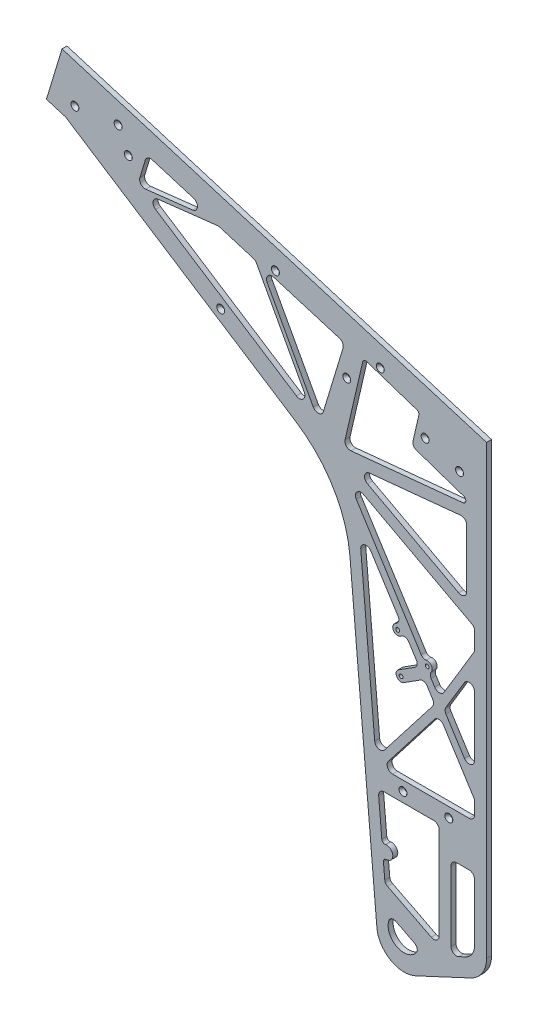
SolidWorks part; units mm, degrees
material "Beech"
ref_plane "Front Plane" through (0, 0, 0) normal (0, 0, 1) x (1, 0, 0)
ref_plane "Top Plane" through (0, 0, 0) normal (0, 1, 0) x (1, 0, 0)
ref_plane "Right Plane" through (0, 0, 0) normal (1, 0, 0) x (0, 0, -1)
sketch "Sketch2" plane through (0, 0, 0) normal (0, 0, 1) x (1, 0, 0)
  line L3 (52.061, -347.2658) -> (17.0528, -329.4943)
  line L18 (0.7275, -204.3995) -> (4.7586, -250.4747)
  line L19 (71, -196.7894) -> (7.7009, -196.7894)
  line L20 (78, -320.9929) -> (78, -203.7894)
  line L21 (8.8549, -297.2958) -> (67.8314, -327.2347)
  line L22 (6.8503, -274.3834) -> (8.8549, -297.2958)
  line L23 (11.4827, -269.9628) -> (10.4865, -270.05)
  line L24 (9.092, -254.1109) -> (10.0882, -254.0237)
  line L27 (123, -309.0696) -> (123, -235.7894)
  line L28 (102.9583, -331.1566) -> (111.4524, -327.1958)
  line L29 (93, -235.7894) -> (93, -324.8124)
  line L30 (116, -228.7894) -> (100, -228.7894)
  line L35 (123, -164.7894) -> (123, -147.491)
  line L36 (18.4936, -171.7894) -> (116, -171.7894)
  line L37 (71.9182, -84.5103) -> (12.9629, -160.4984)
  line L38 (123, -147.491) -> (83.3585, -85.0495)
  line L41 (123, -104.7468) -> (123, -28.6549)
  line L42 (86.5792, -71.4649) -> (110.0903, -108.4986)
  line L43 (110.0027, -25.0448) -> (86.4916, -64.103)
  line L47 (-22.0887, 56.3913) -> (-4.3233, -146.6681)
  line L48 (69.6883, -63.5168) -> (-9.2057, 60.7532)
  line L49 (8.1807, -150.3489) -> (69.3092, -71.5595)
  line L55 (84.1071, -48.674) -> (123, 15.9373)
  line L56 (-27.7256, 108.5825) -> (72.2002, -48.8158)
  line L57 (123, 42.7347) -> (-18.5117, 118.5054)
  line L58 (123, 15.9373) -> (123, 42.7347)
  line L61 (105.3136, 157.4535) -> (-10.9295, 145.9995)
  line L62 (113, 76.7923) -> (113, 150.4873)
  line L63 (-13.5473, 132.8622) -> (102.6958, 70.6213)
  line L71 (49.3928, 246.173) -> (-14.4833, 267.3378)
  line L72 (43.1791, 203.129) -> (52.0322, 241.4762)
  line L73 (109.2468, 180.5917) -> (43.1791, 203.129)
  line L74 (-34.5621, 158.7435) -> (108.3476, 172.8251)
  line L75 (-19.6388, 264.4406) -> (-42.0691, 167.2844)
  line L99 (-35.9297, 42.1538) -> (-1.5139, -351.2208)
  line L100 (48.0382, -379.8296) -> (118.2139, -347.1062)
  line L101 (138.3789, -315.4534) -> (138.3789, 254.5381)
  line L102 (138.3789, 254.5381) -> (-403.0991, 418.4193)
  line L103 (-403.0991, 418.4193) -> (-422.935, 352.8794)
  line L104 (-422.935, 352.8794) -> (-398.6241, 345.5216)
  line L105 (-398.6241, 345.5216) -> (-105.0266, 156.03)
  line L106 (-35.9297, 42.1538) -> (-1.5139, -351.2208)
  line L107 (48.0382, -379.8296) -> (118.2139, -347.1062)
  line L108 (138.3789, -315.4534) -> (138.3789, 254.5381)
  line L109 (138.3789, 254.5381) -> (-403.0991, 418.4193)
  line L110 (-403.0991, 418.4193) -> (-422.935, 352.8794)
  line L111 (-422.935, 352.8794) -> (-398.6241, 345.5216)
  line L112 (-398.6241, 345.5216) -> (-105.0266, 156.03)
  arc A2 (17.0528, -329.4943) -> (52.061, -347.2658) centre (32.8243, -341.7931) ccw
  arc A14 (4.7586, -250.4747) -> (9.092, -254.1109) centre (8.7434, -250.1261) ccw
  arc A15 (7.7009, -196.7894) -> (0.7275, -204.3995) centre (7.7009, -203.7894) ccw
  arc A16 (78, -203.7894) -> (71, -196.7894) centre (71, -203.7894) ccw
  arc A17 (67.8314, -327.2347) -> (78, -320.9929) centre (71, -320.9929) ccw
  arc A18 (10.4865, -270.05) -> (6.8503, -274.3834) centre (10.8351, -274.0347) ccw
  arc A19 (11.4827, -269.9628) -> (10.0882, -254.0237) centre (10.7854, -261.9933) ccw
  arc A22 (123, -235.7894) -> (116, -228.7894) centre (116, -235.7894) ccw
  arc A23 (111.4524, -327.1958) -> (123, -309.0696) centre (103, -309.0696) ccw
  arc A24 (93, -324.8124) -> (102.9583, -331.1566) centre (100, -324.8124) ccw
  arc A25 (100, -228.7894) -> (93, -235.7894) centre (100, -235.7894) ccw
  arc A28 (116, -171.7894) -> (123, -164.7894) centre (116, -164.7894) ccw
  arc A29 (12.9629, -160.4984) -> (18.4936, -171.7894) centre (18.4936, -164.7894) ccw
  arc A30 (83.3585, -85.0495) -> (71.9182, -84.5103) centre (77.4488, -88.8013) ccw
  arc A34 (110.0903, -108.4986) -> (123, -104.7468) centre (116, -104.7468) ccw
  arc A35 (86.4916, -64.103) -> (86.5792, -71.4649) centre (92.4888, -67.7131) ccw
  arc A36 (123, -28.6549) -> (110.0027, -25.0448) centre (116, -28.6549) ccw
  arc A40 (-4.3233, -146.6681) -> (8.1807, -150.3489) centre (2.65, -146.058) ccw
  arc A41 (-9.2057, 60.7532) -> (-22.0887, 56.3913) centre (-15.1153, 57.0014) ccw
  arc A42 (69.3092, -71.5595) -> (69.6883, -63.5168) centre (63.7786, -67.2686) ccw
  arc A44 (72.2002, -48.8158) -> (84.1071, -48.674) centre (78.1098, -45.064) ccw
  arc A45 (-18.5117, 118.5054) -> (-27.7256, 108.5825) centre (-21.8159, 112.3343) ccw
  arc A50 (113, 150.4873) -> (105.3136, 157.4535) centre (106, 150.4873) ccw
  arc A51 (102.6958, 70.6213) -> (113, 76.7923) centre (106, 76.7923) ccw
  arc A52 (-10.9295, 145.9995) -> (-13.5473, 132.8622) centre (-10.2431, 139.0332) ccw
  arc A58 (-14.4833, 267.3378) -> (-19.6388, 264.4406) centre (-15.7414, 263.5408) ccw
  arc A59 (52.0322, 241.4762) -> (49.3928, 246.173) centre (48.1347, 242.376) ccw
  arc A60 (108.3476, 172.8251) -> (109.2468, 180.5917) centre (107.9554, 176.8059) ccw
  arc A61 (-42.0691, 167.2844) -> (-34.5621, 158.7435) centre (-35.2485, 165.7098) ccw
  arc A77 (-35.9297, 42.1538) -> (-105.0266, 156.03) centre (-187.6695, 27.9835) ccw
  arc A78 (-1.5139, -351.2208) -> (48.0382, -379.8296) centre (33.2782, -348.1768) ccw
  arc A79 (118.2139, -347.1062) -> (138.3789, -315.4534) centre (103.4539, -315.4534) ccw
  arc A80 (-35.9297, 42.1538) -> (-105.0266, 156.03) centre (-187.6695, 27.9835) ccw
  arc A81 (-1.5139, -351.2208) -> (48.0382, -379.8296) centre (33.2782, -348.1768) ccw
  arc A82 (118.2139, -347.1062) -> (138.3789, -315.4534) centre (103.4539, -315.4534) ccw
  line B0 (-69.7843, 184.37) -> (-44.7069, 267.0652)
  line B1 (-141.4417, 291.191) -> (-82.6325, 183.0571)
  line B2 (-49.3742, 275.7954) -> (-133.2609, 301.2341)
  line B3 (-94.2196, 193.8972) -> (-156.4138, 308.2553)
  line B4 (-283.8496, 300.7813) -> (-104.1681, 184.6735)
  line B5 (-203.4472, 322.5182) -> (-280.8504, 313.6148)
  line B6 (-156.4138, 308.2553) -> (-203.4472, 322.5182)
  line B7 (-235.2905, 337.3996) -> (-288.1216, 353.4207)
  line B8 (-296.2966, 316.871) -> (-236.522, 323.7467)
  line B9 (-296.8518, 348.7534) -> (-303.7953, 325.8566)
  arc B10 (-44.7069, 267.0652) -> (-49.3742, 275.7954) centre (-51.4056, 269.0966) ccw
  arc B11 (-82.6325, 183.0571) -> (-69.7843, 184.37) centre (-76.4831, 186.4014) ccw
  arc B12 (-133.2609, 301.2341) -> (-141.4417, 291.191) centre (-135.2923, 294.5354) ccw
  arc B13 (-104.1681, 184.6735) -> (-94.2196, 193.8972) centre (-100.369, 190.5528) ccw
  arc B14 (-280.8504, 313.6148) -> (-283.8496, 300.7813) centre (-280.0505, 306.6606) ccw
  arc B15 (-236.522, 323.7467) -> (-235.2905, 337.3996) centre (-237.3219, 330.7009) ccw
  arc B16 (-303.7953, 325.8566) -> (-296.2966, 316.871) centre (-297.0965, 323.8251) ccw
  arc B17 (-288.1216, 353.4207) -> (-296.8518, 348.7534) centre (-290.153, 346.7219) ccw
  dimension "D13" = 0
sketch_block_instance "Block1-1"
sketch_block "Block1" parameters "D4"=7, "D1"=23.432, "D2"=23.9265, "D3"=55.2069
extrude "Boss-Extrude1" add sketch "Sketch2" along normal blind 6.35
sketch "Sketch3" plane through (0, 0, 6.35) normal (0, 0, 1) x (1, 0, 0)
  line L25 (32.2931, -4.6137) -> (25.0263, -9.2271) construction
  line L26 (69.6883, -63.5168) -> (-9.2057, 60.7532) construction
  line L27 (35.6965, -9.9746) -> (28.4297, -14.588)
  line L28 (28.8896, 0.7472) -> (21.6228, -3.8662)
  line L29 (29.3174, -58.2747) -> (55.7191, -41.5133) construction
  line L30 (25.914, -52.9138) -> (52.3157, -36.1524)
  line L31 (32.7208, -63.6356) -> (59.1225, -46.8742)
  line L32 (62.6488, -30.6471) -> (61.2353, -31.5444) construction
  line L33 (-27.7256, 108.5825) -> (72.2002, -48.8158) construction
  line L34 (66.0522, -36.008) -> (64.6387, -36.9053)
  line L35 (59.2454, -25.2862) -> (57.8319, -26.1835)
  arc A13 (35.6965, -9.9746) -> (28.8896, 0.7472) centre (32.2931, -4.6137) ccw
  arc A14 (21.6228, -3.8662) -> (28.4297, -14.588) centre (25.0263, -9.2271) ccw
  arc A15 (25.914, -52.9138) -> (32.7208, -63.6356) centre (29.3174, -58.2747) ccw
  arc A16 (59.1225, -46.8742) -> (52.3157, -36.1524) centre (55.7191, -41.5133) ccw
  arc A17 (66.0522, -36.008) -> (59.2454, -25.2862) centre (62.6488, -30.6471) ccw
  arc A18 (57.8319, -26.1835) -> (64.6387, -36.9053) centre (61.2353, -31.5444) ccw
  point P6 (28.6597, -6.9204)
  point P13 (42.5182, -49.894)
  point P20 (61.942, -31.0957)
  dimension "D2" = 6.35
extrude "Boss-Extrude3" add sketch "Sketch3" against normal through all contours A18 A16 L30 A15 L31 | L35 A18 A16 L34 A17 | L28 A14 L27 A13 region at (28.6597, -6.9204, 6.35) region at (42.3663, -50.0213, 6.35) region at (62.0617, -30.908, 6.35)
fillet "Fillet2" radius 6.35 15 edges at (-203.4472, 322.5182, 3.175) (-156.4138, 308.2553, 3.175) (43.1791, 203.129, 3.175) (123, 42.7347, 3.175) (123, 15.9373, 3.175) (123, -147.491, 3.175) (8.8549, -297.2958, 3.175) (17.0528, -329.4943, 3.175) (52.061, -347.2658, 3.175) (64.6387, -36.9053, 3.175) (57.8319, -26.1835, 3.175) (28.8896, 0.7472, 3.175) (35.6965, -9.9746, 3.175) (52.3157, -36.1524, 3.175) (59.1225, -46.8742, 3.175)
hole_wizard "#8 Clearance Hole1" positions "Sketch4" profile "Sketch5" hole size "#8" standard "ANSI Inch" end condition up to next
sketch "Sketch4" plane through (0, 0, 6.35) normal (0, 0, 1) x (1, 0, 0)
  circle A0 centre (25.0263, -9.2271) radius 2.4574 construction
  circle A1 centre (29.3174, -58.2747) radius 2.4574 construction
  circle A2 centre (62.6488, -30.6471) radius 2.4574 construction
  point P0 (62.6488, -30.6471)
  point P2 (29.3174, -58.2747)
  point P4 (25.0263, -9.2271)
sketch "Sketch5" plane through (62.6488, -30.6471, 6.35) normal (1, 0, 0) x (0, -1, 0)
  line L0 (0, 0) -> (0, 6.35)
  line L1 (0, 6.35) -> (2.4574, 6.35)
  line L2 (2.4574, 6.35) -> (2.4574, 0)
  line L5 (2.4574, 0) -> (0, 0)
  line L11 (0, -6.35) -> (0, 107.95) construction
  dimension "Thru Hole Dia." = 4.9149
  dimension "Thru Hole Depth" = 6.35
hole_wizard "Hole1" positions "Sketch6" profile "Sketch7" legacy
sketch "Sketch6" plane through (277.2867, -215.2871, 6.35) normal (0, 0, 1) x (-0.09, 0.9959, 0)
  line L0 (54.6742, 260.7254) -> (44.8416, 151.8686) construction
  line L6 (458.2175, 188.8136) -> (426.7882, 117.3689) construction
  line L11 (443.4217, 288.0956) -> (513.4071, 262.4897) construction
  line L16 (479.186, 443.3317) -> (498.5551, 428.1819) construction
  line L19 (643.2075, 626.7743) -> (602.3132, 525.5573) construction
  line L24 (664.0363, 618.3589) -> (454.7061, 100.2486) construction
  line L28 (664.0363, 618.3589) -> (611.7037, 488.8313)
  line L29 (611.7037, 488.8313) -> (559.3712, 359.3037)
  line L30 (559.3712, 359.3037) -> (507.0387, 229.7761)
  line L31 (507.0387, 229.7761) -> (454.7061, 100.2486)
  point P12 (52.9605, 241.7526)
  point P14 (47.6978, 183.4898)
  point P29 (434.4591, 134.8062)
  point P31 (453.1036, 177.1887)
  point P48 (478.4144, 275.2927)
  point P60 (488.8705, 435.7568)
  point P79 (636.0712, 609.1114)
  point P81 (609.4494, 543.2202)
  point P98 (559.3712, 359.3037)
  point P100 (507.0387, 229.7761)
  point P112 (637.87, 553.5951)
sketch "Sketch7" plane through (-331.4463, 370.1954, 6.35) normal (1, 0, 0) x (0, -1, 0)
  line L0 (0, 0) -> (0, 32.7039)
  line L1 (0, 32.7039) -> (1.5875, 31.75)
  line L2 (1.5875, 31.75) -> (1.5875, 4.0177)
  line L3 (1.5875, 4.0177) -> (5.08, 0)
  line L4 (5.08, 0) -> (0, 0)
  line L5 (0, -14.3089) -> (0, 102.4216) construction
  line L6 (0, 32.7039) -> (-1.5875, 31.75) construction
  line L7 (-1.5875, 4.0177) -> (-5.08, 0) construction
  dimension "Diameter" = 3.175
  dimension "Depth" = 31.75
  dimension "C-Sink Diameter" = 10.16
  dimension "C-Sink Angle" = 82
  dimension "Drill Angle" = 118
